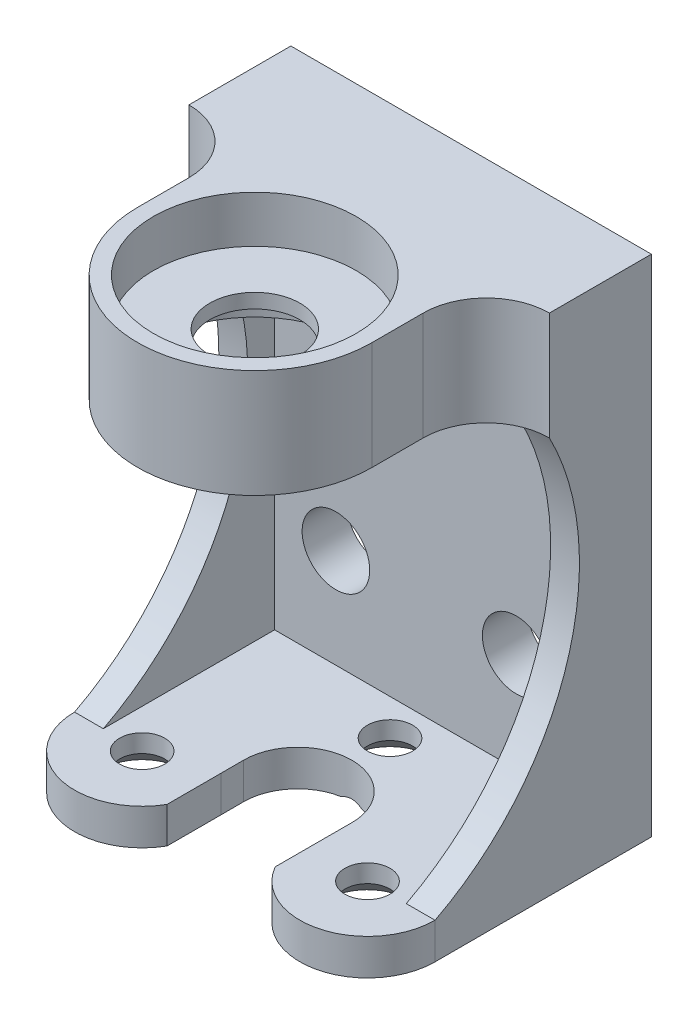
SolidWorks part; units mm, degrees
ref_plane "Front Plane" through (0, 0, 0) normal (0, 0, 1) x (1, 0, 0)
ref_plane "Top Plane" through (0, 0, 0) normal (0, 1, 0) x (1, 0, 0)
ref_plane "Right Plane" through (0, 0, 0) normal (1, 0, 0) x (0, 0, -1)
sketch "Sketch1" plane through (0, 0, 0) normal (0, 0, 1) x (1, 0, 0)
  line L0 (0, 29.21) -> (0, -6.35) construction
  line L1 (-12.7, 29.21) -> (12.7, 29.21)
  line L2 (-12.7, 29.21) -> (-12.7, -6.35)
  line L3 (-12.7, -6.35) -> (12.7, -6.35)
  line L4 (12.7, 29.21) -> (12.7, -6.35)
  circle A0 centre (-6.35, 3.175) radius 2.3813
  circle A1 centre (6.35, 3.175) radius 2.3813
  point P0 (0, 0)
  dimension "D4" = 12.7
  dimension "D1" = 12.7
  dimension "D2" = 35.56
  dimension "D3" = 12.7
  dimension "D5" = 6.35
  dimension "D6" = 6.35
extrude "Boss-Extrude1" add sketch "Sketch1" along normal blind 3.175
sketch "Sketch7" plane through (0, 0, 3.175) normal (0, 0, 1) x (1, 0, 0)
  line L0 (0, -2.6536) -> (0, 2.4264) construction
  line L1 (-12.7, -3.81) -> (12.7, -3.81)
  line L2 (-12.7, -3.81) -> (-12.7, -6.35)
  line L3 (-12.7, -6.35) -> (12.7, -6.35)
  line L4 (12.7, -3.81) -> (12.7, -6.35)
  line L5 (-12.7, -3.81) -> (12.7, -6.35) construction
  line L6 (-12.7, -6.35) -> (12.7, -3.81) construction
  line L7 (-12.7, -6.35) -> (12.7, -6.35) construction
  line L8 (12.7, -6.35) -> (12.7, 29.21) construction
  line L9 (-12.7, 21.59) -> (12.7, 21.59)
  line L10 (-12.7, 21.59) -> (-12.7, 29.21)
  line L11 (-12.7, 29.21) -> (12.7, 29.21)
  line L12 (12.7, 21.59) -> (12.7, 29.21)
  line L13 (-12.7, 21.59) -> (12.7, 29.21) construction
  line L14 (-12.7, 29.21) -> (12.7, 21.59) construction
  line L15 (12.7, 29.21) -> (-12.7, 29.21) construction
  point P0 (0, -5.08)
  point P7 (0, 25.4)
  dimension "D1" = 2.54
  dimension "D2" = 7.62
  dimension "1" = 25.4
  dimension "D3" = 3.81
  dimension "D4" = 25.4
extrude "Boss-Extrude3" add sketch "Sketch7" along normal blind 20.32
sketch "Sketch11" plane through (0, -6.35, 0) normal (0, -1, 0) x (1, 0, 0)
  line L0 (12.7, 23.495) -> (12.7, 0) construction
  line L1 (-3.8147, 12.219) -> (-3.81, 13.806)
  line L2 (-12.7, 15.24) -> (12.7, 15.24) construction
  line L3 (3.8147, 12.219) -> (3.81, 13.806)
  line L4 (-12.7, 23.495) -> (12.7, 23.495) construction
  line L5 (-12.7, 23.495) -> (-12.7, 0) construction
  line L7 (0, 23.495) -> (0, 12.219) construction
  line L8 (3.81, 17.616) -> (3.81, 13.806)
  line L9 (-12.7, 23.495) -> (12.7, 23.495) construction
  line L10 (-3.81, 17.616) -> (-3.81, 13.806)
  circle A0 centre (-7.9375, 15.24) radius 1.5875
  circle A1 centre (7.9375, 15.24) radius 1.5875
  arc A2 (12.7, 15.24) -> (3.81, 17.616) centre (7.9375, 15.24) ccw
  circle A3 centre (0, 5.715) radius 1.5875
  arc A4 (-3.8146, 12.2415) -> (3.8146, 12.2415) centre (0, 12.219) ccw
  arc A5 (-12.7, 15.24) -> (-3.81, 17.616) centre (-7.9375, 15.24) cw
  point P17 (-12.3447, 26.9875)
  point P26 (12.3447, 26.9875)
  line M5 (12.7, 0) -> (12.7, 23.495)
  line M6 (12.7, 23.495) -> (-12.7, 23.495)
  line M7 (-12.7, 23.495) -> (-12.7, 0)
  dimension "D3" = 1.587
  dimension "D2" = 3.8147
  dimension "D5" = 3.175
  dimension "D6" = 4.7625
  dimension "D7" = 3.175
  dimension "D1" = 8.89
  dimension "D4" = 9.525
  dimension "D8" = 1.587
  dimension "D9" = 3.81
  dimension "D10" = 11.276
extrude "Cut-Extrude1" cut sketch "Sketch11" against normal blind 10 contours A0 | A1 | A3 | A5 L10 L8 A2 M7 M5 M6 region at (0, -6.35, 18.3653) region at (-7.9375, -6.35, 15.24) region at (7.9375, -6.35, 15.24) region at (0, -6.35, 5.715)
chamfer "Chamfer2" distance 1.27 angle 45 3 edges at (9.525, -6.35, 15.24) (1.5875, -6.35, 5.715) (-6.35, -6.35, 15.24)
sketch "Sketch13" plane through (0, 29.21, 0) normal (0, 1, 0) x (1, 0, 0)
  line L0 (12.7, 0) -> (-12.7, 0) construction
  line L1 (12.7, -23.495) -> (12.7, 0) construction
  circle A0 centre (0, -15.24) radius 3.175
  dimension "D1" = 6.35
  dimension "D2" = 15.24
  dimension "D3" = 12.7
extrude "Cut-Extrude2" cut sketch "Sketch13" against normal blind 12.7
sketch "Sketch14" plane through (0, 29.21, 0) normal (0, 1, 0) x (1, 0, 0)
  circle A0 centre (0, -15.24) radius 7.1438
  circle A1 centre (0, -15.24) radius 3.175 construction
  dimension "D1" = 14.2875
extrude "Cut-Extrude3" cut sketch "Sketch14" against normal blind 3.302
sketch "Sketch15" plane through (0, 21.59, 0) normal (0, -1, 0) x (1, 0, 0)
  circle A0 centre (0, 15.24) radius 7.1438
  circle A1 centre (0, 15.24) radius 3.175 construction
  dimension "D1" = 14.2875
extrude "Cut-Extrude4" cut sketch "Sketch15" against normal blind 3.302
sketch "Sketch16" plane through (0, 29.21, 0) normal (0, 1, 0) x (1, 0, 0)
  line L0 (-8.255, -15.24) -> (-8.255, -11.6294)
  line L2 (8.255, -15.24) -> (8.255, -11.6294)
  line L3 (-12.7, -23.495) -> (-12.7, 0) construction
  line L4 (12.7, -23.495) -> (12.7, 0) construction
  line L5 (12.7, -7.1844) -> (12.7, -23.495)
  line L6 (12.7, -23.495) -> (-12.7, -23.495)
  line L7 (-12.7, -23.495) -> (-12.7, -7.1844)
  line L8 (12.7, 0) -> (-12.7, 0) construction
  arc A0 (-8.255, -15.24) -> (8.255, -15.24) centre (0, -15.24) ccw
  arc A1 (-8.255, -11.6294) -> (-12.7, -7.1844) centre (-12.7, -11.6294) ccw
  arc A2 (12.7, -7.1844) -> (8.255, -11.6294) centre (12.7, -11.6294) ccw
  line M3 (-12.7, 0) -> (-12.7, -23.495)
  line M4 (-12.7, -23.495) -> (12.7, -23.495)
  line M5 (12.7, -23.495) -> (12.7, 0)
  dimension "D1" = 8.255
  dimension "D2" = 11.6294
  dimension "D3" = 11.6294
extrude "Cut-Extrude5" cut sketch "Sketch16" against normal blind 12.7 contours A2 L2 A0 L6 M5 | L0 A1 A0 M3 M4 region at (-9.8229, 29.21, 16.8197) region at (9.8229, 29.21, 16.8197)
sketch "Sketch17" plane through (0, 0, 3.175) normal (0, 0, 1) x (1, 0, 0)
  line L0 (12.7, -3.81) -> (-12.7, -3.81) construction
  line L1 (12.7, 21.59) -> (10.671, 21.59)
  line L2 (12.7, 21.59) -> (12.7, -3.81)
  line L3 (12.7, -3.81) -> (10.671, -3.81)
  line L4 (10.671, 21.59) -> (10.671, -3.81)
  line L5 (0, 0) -> (0, 8.4961) construction
  line L6 (-10.671, 21.59) -> (-10.671, -3.81)
  line M4 (12.7, -3.81) -> (12.7, 21.59)
  line M5 (12.7, 21.59) -> (-12.7, 21.59)
  line M6 (-12.7, 21.59) -> (-12.7, -3.81)
  line M7 (-12.7, -3.81) -> (12.7, -3.81)
  dimension "D1" = 2.029
  dimension "D2" = 10.671
extrude "Boss-Extrude4" add sketch "Sketch17" along normal blind 12.7 contours L6 M5 M6 M7 | L4 M5 M7 M4 region at (11.6855, 8.89, 3.175) region at (-11.6855, 8.89, 3.175)
sketch "Sketch18" plane through (12.7, 0, 0) normal (1, 0, 0) x (0, 0, -1)
  arc A0 (-7.1844, 21.59) -> (-15.24, -3.81) centre (-23.9122, 12.9178) cw
  line M2 (-7.1844, 21.59) -> (-15.875, 21.59)
  line M3 (-15.875, 21.59) -> (-15.875, -3.81)
  line M4 (-15.875, -3.81) -> (-15.24, -3.81)
  dimension "D1" = 18.8421
extrude "Cut-Extrude6" cut sketch "Sketch18" against normal through all contours A0 M2 M3 M4 region at (12.7, 10.5489, 11.1727)
